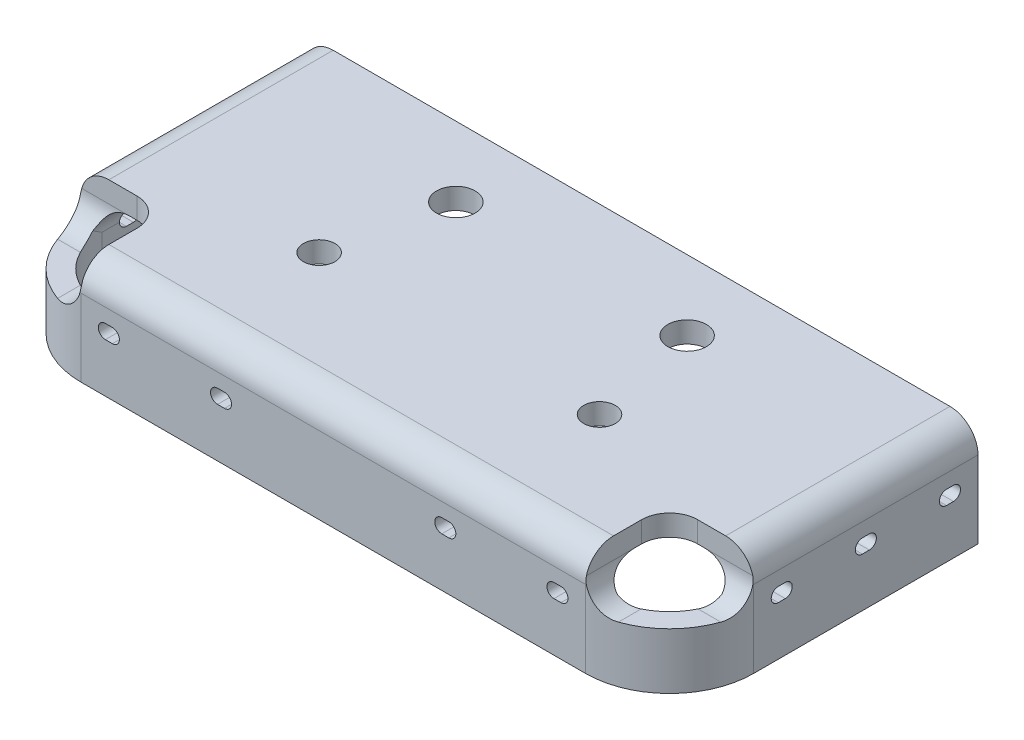
SolidWorks part; units mm, degrees
ref_plane "Front Plane" through (0, 0, 0) normal (0, 0, 1) x (1, 0, 0)
ref_plane "Top Plane" through (0, 0, 0) normal (0, 1, 0) x (1, 0, 0)
ref_plane "Right Plane" through (0, 0, 0) normal (1, 0, 0) x (0, 0, -1)
sketch "Sketch1" plane through (0, 0, 0) normal (0, 1, 0) x (1, 0, 0)
  line L0 (-41.275, 0) -> (41.275, 0) construction
  line L5 (-41.275, 25.4) -> (41.275, 25.4)
  line L6 (-41.275, 25.4) -> (-41.275, -25.4) construction
  line L7 (-41.275, -25.4) -> (41.275, -25.4) construction
  line L8 (41.275, 25.4) -> (41.275, -25.4) construction
  line L9 (-76.2, 25.4) -> (-76.2, -25.4)
  line L10 (-57.15, -44.45) -> (57.15, -44.45)
  line L11 (76.2, -25.4) -> (76.2, 25.4)
  line L12 (0, -25.4) -> (0, -44.45) construction
  line L13 (-41.275, 0) -> (-76.2, 0) construction
  line L14 (41.275, 0) -> (76.2, 0) construction
  line L15 (-41.275, 25.4) -> (-76.2, 25.4)
  line L16 (41.275, 25.4) -> (76.2, 25.4)
  line L17 (57.15, -44.45) -> (57.15, -25.4)
  line L18 (57.15, -25.4) -> (76.2, -25.4)
  line L19 (-76.2, -25.4) -> (-57.15, -25.4)
  line L20 (-57.15, -25.4) -> (-57.15, -44.45)
  arc A0 (-76.2, -25.4) -> (-57.15, -44.45) centre (-57.15, -25.4) ccw construction
  arc A1 (57.15, -44.45) -> (76.2, -25.4) centre (57.15, -25.4) ccw construction
  dimension "D4" = 19.05
  dimension "D1" = 50.8
  dimension "D2" = 152.4
  dimension "D3" = 69.85
  dimension "D5" = 82.55
extrude "Boss-Extrude1" add sketch "Sketch1" along normal blind 4.7625
sketch "Sketch9" plane through (0, 4.7625, 0) normal (0, 1, 0) x (1, 0, 0)
  line L0 (0, 9.525) -> (0, -15.875) construction
  line L1 (-31.75, -15.875) -> (31.75, -15.875) construction
  line L2 (-26.1937, 9.525) -> (26.1937, 9.525) construction
  point P7 (0, 0)
  point P8 (0, 0)
  dimension "D1" = 15.875
  dimension "D2" = 9.525
  dimension "D3" = 52.3875
  dimension "D4" = 63.5
hole_wizard "5/16 Clearance Hole1" positions "Sketch10" profile "Sketch11" hole size "5/16" standard "ANSI Inch" end condition through all
sketch "Sketch10" plane through (0, 4.7625, 0) normal (0, 1, 0) x (1, 0, 0)
  point P0 (-26.1937, 9.525)
  point P3 (26.1937, 9.525)
sketch "Sketch11" plane through (-26.1937, 4.7625, -9.525) normal (1, 0, 0) x (0, 0, 1)
  line L0 (0, 0) -> (0, 4.7625)
  line L1 (0, 4.7625) -> (4.365, 4.7625)
  line L2 (4.365, 4.7625) -> (4.365, 0)
  line L5 (4.365, 0) -> (0, 0)
  line L11 (0, -6.35) -> (0, 107.95) construction
  dimension "Thru Hole Dia." = 8.73
  dimension "Thru Hole Depth" = 4.7625
hole_wizard "1/4 Clearance Hole1" positions "Sketch12" profile "Sketch13" hole size "1/4" standard "ANSI Inch" end condition through all
sketch "Sketch12" plane through (0, 4.7625, 0) normal (0, 1, 0) x (1, 0, 0)
  point P0 (-31.75, -15.875)
  point P3 (31.75, -15.875)
sketch "Sketch13" plane through (-31.75, 4.7625, 15.875) normal (1, 0, 0) x (0, 0, 1)
  line L0 (0, 0) -> (0, 4.7625)
  line L1 (0, 4.7625) -> (3.5712, 4.7625)
  line L2 (3.5712, 4.7625) -> (3.5712, 0)
  line L5 (3.5712, 0) -> (0, 0)
  line L11 (0, -6.35) -> (0, 107.95) construction
  dimension "Thru Hole Dia." = 7.1425
  dimension "Thru Hole Depth" = 4.7625
sketch "Sketch2" plane through (0, 0, 0) normal (0, 1, 0) x (1, 0, 0)
  line L0 (76.2, -25.4) -> (76.2, 25.4) construction
  line L1 (-57.15, -44.45) -> (57.15, -44.45) construction
  line L2 (-76.2, 25.4) -> (-76.2, -25.4) construction
  line L3 (76.2, -25.4) -> (76.2, 25.4)
  line L4 (-57.15, -44.45) -> (57.15, -44.45)
  line L5 (-76.2, 25.4) -> (-76.2, -25.4)
  line L6 (-71.4375, 25.4) -> (-71.4375, -25.4)
  line L7 (-57.15, -39.6875) -> (57.15, -39.6875)
  line L8 (71.4375, -25.4) -> (71.4375, 25.4)
  line L9 (-76.2, 25.4) -> (-71.4375, 25.4)
  line L10 (76.2, 25.4) -> (71.4375, 25.4)
  arc A0 (57.15, -44.45) -> (76.2, -25.4) centre (57.15, -25.4) ccw construction
  arc A1 (-76.2, -25.4) -> (-57.15, -44.45) centre (-57.15, -25.4) ccw construction
  arc A2 (57.15, -44.45) -> (76.2, -25.4) centre (57.15, -25.4) ccw
  arc A3 (-76.2, -25.4) -> (-57.15, -44.45) centre (-57.15, -25.4) ccw
  arc A4 (-71.4375, -25.4) -> (-57.15, -39.6875) centre (-57.15, -25.4) ccw
  arc A5 (57.15, -39.6875) -> (71.4375, -25.4) centre (57.15, -25.4) ccw
  dimension "D1" = 4.7625
extrude "Boss-Extrude2" add sketch "Sketch2" against normal blind 19.05
sketch "Sketch18" plane through (0, 0, 0) normal (0, 1, 0) x (1, 0, 0)
  line L0 (76.2, -25.4) -> (71.4375, -25.4) construction
  line L1 (57.15, -39.6875) -> (57.15, -44.45) construction
  line L2 (-57.15, -44.45) -> (-57.15, -39.6875) construction
  line L3 (-71.4375, -25.4) -> (-76.2, -25.4) construction
  line L4 (76.2, -25.4) -> (71.4375, -25.4)
  line L5 (57.15, -39.6875) -> (57.15, -44.45)
  line L6 (-57.15, -44.45) -> (-57.15, -39.6875)
  line L7 (-71.4375, -25.4) -> (-76.2, -25.4)
  arc A0 (57.15, -39.6875) -> (71.4375, -25.4) centre (57.15, -25.4) ccw construction
  arc A1 (57.15, -44.45) -> (76.2, -25.4) centre (57.15, -25.4) ccw construction
  arc A2 (-71.4375, -25.4) -> (-57.15, -39.6875) centre (-57.15, -25.4) ccw construction
  arc A3 (-76.2, -25.4) -> (-57.15, -44.45) centre (-57.15, -25.4) ccw construction
  arc A4 (57.15, -39.6875) -> (71.4375, -25.4) centre (57.15, -25.4) ccw
  arc A5 (57.15, -44.45) -> (76.2, -25.4) centre (57.15, -25.4) ccw
  arc A6 (-71.4375, -25.4) -> (-57.15, -39.6875) centre (-57.15, -25.4) ccw
  arc A7 (-76.2, -25.4) -> (-57.15, -44.45) centre (-57.15, -25.4) ccw
extrude "Cut-Extrude3" cut sketch "Sketch18" against normal offset from surface (6.35 mm away) 12.7 up to face at (0, -19.05, 15.1737)
fillet "Fillet4" radius 6.35 8 edges at (-76.2, 4.7625, 0) (76.2, 4.7625, 0) (0, 4.7625, 44.45) (71.4375, 0, 0) (-71.4375, 0, 0) (0, 0, 39.6875) (-57.15, 2.3813, 25.4) (57.15, 2.3813, 25.4)
fillet "Fillet5" radius 6.35 4 edges at (73.8188, -6.35, 25.4) (-57.15, -6.35, 42.0687) (-73.8188, -6.35, 25.4) (57.15, -6.35, 42.0687)
sketch "Sketch15" plane through (0, 0, 0) normal (1, 0, 0) x (0, 0, -1)
  line L0 (-18.2563, -6.35) -> (-19.8438, -6.35) construction
  line L1 (-18.2563, -7.9375) -> (-19.8438, -7.9375)
  line L2 (-18.2563, -4.7625) -> (-19.8438, -4.7625)
  line L3 (-25.4, -19.05) -> (25.4, -19.05) construction
  line L4 (0.7937, -6.35) -> (-0.7937, -6.35) construction
  line L5 (0.7937, -7.9375) -> (-0.7937, -7.9375)
  line L6 (0.7937, -4.7625) -> (-0.7937, -4.7625)
  line L7 (19.8438, -6.35) -> (18.2563, -6.35) construction
  line L8 (19.8438, -7.9375) -> (18.2563, -7.9375)
  line L9 (19.8438, -4.7625) -> (18.2563, -4.7625)
  arc A0 (-18.2563, -7.9375) -> (-18.2563, -4.7625) centre (-18.2563, -6.35) ccw
  arc A1 (-19.8438, -4.7625) -> (-19.8438, -7.9375) centre (-19.8438, -6.35) ccw
  arc A2 (0.7937, -7.9375) -> (0.7937, -4.7625) centre (0.7937, -6.35) ccw
  arc A3 (-0.7937, -4.7625) -> (-0.7937, -7.9375) centre (-0.7937, -6.35) ccw
  arc A4 (19.8438, -7.9375) -> (19.8438, -4.7625) centre (19.8438, -6.35) ccw
  arc A5 (18.2563, -4.7625) -> (18.2563, -7.9375) centre (18.2563, -6.35) ccw
  point P2 (-19.05, -6.35)
  point P10 (19.8438, -4.7625)
  point P13 (0, -6.35)
  point P20 (19.05, -6.35)
  point P25 (0, 0)
  dimension "D1" = 1.5875
  dimension "D2" = 1.5875
  dimension "D3" = 19.05
  dimension "D4" = 12.7
  dimension "D5" = 3
extrude "Cut-Extrude1" cut sketch "Sketch15" against normal through all both and the other way through all
sketch "Sketch16" plane through (0, 0, 0) normal (0, 0, 1) x (1, 0, 0)
  line L0 (-51.5938, -6.35) -> (-50.0062, -6.35) construction
  line L1 (-51.5938, -4.7625) -> (-50.0062, -4.7625)
  line L2 (-51.5938, -7.9375) -> (-50.0062, -7.9375)
  line L3 (-57.15, -19.05) -> (57.15, -19.05) construction
  line L4 (-26.1938, -6.35) -> (-24.6062, -6.35) construction
  line L5 (-26.1938, -4.7625) -> (-24.6062, -4.7625)
  line L6 (-26.1938, -7.9375) -> (-24.6062, -7.9375)
  line L10 (24.6062, -6.35) -> (26.1937, -6.35) construction
  line L11 (24.6062, -4.7625) -> (26.1937, -4.7625)
  line L12 (24.6062, -7.9375) -> (26.1937, -7.9375)
  line L13 (50.0062, -6.35) -> (51.5938, -6.35) construction
  line L14 (50.0062, -4.7625) -> (51.5938, -4.7625)
  line L15 (50.0062, -7.9375) -> (51.5937, -7.9375)
  line L64 (-0.7938, -6.35) -> (0.7938, -6.35) construction
  line L65 (-0.7938, -4.7625) -> (0.7938, -4.7625)
  line L66 (-0.7938, -7.9375) -> (0.7938, -7.9375)
  line L67 (-0.7938, -6.35) -> (0.7938, -6.35) construction
  line L68 (-0.7938, -4.7625) -> (0.7938, -4.7625)
  line L69 (-0.7938, -7.9375) -> (0.7937, -7.9375)
  arc A0 (-51.5938, -4.7625) -> (-51.5938, -7.9375) centre (-51.5938, -6.35) ccw
  arc A1 (-50.0062, -7.9375) -> (-50.0062, -4.7625) centre (-50.0062, -6.35) ccw
  arc A2 (-26.1938, -4.7625) -> (-26.1938, -7.9375) centre (-26.1938, -6.35) ccw
  arc A3 (-24.6062, -7.9375) -> (-24.6062, -4.7625) centre (-24.6062, -6.35) ccw
  arc A6 (24.6062, -4.7625) -> (24.6062, -7.9375) centre (24.6062, -6.35) ccw
  arc A7 (26.1937, -7.9375) -> (26.1937, -4.7625) centre (26.1937, -6.35) ccw
  arc A8 (50.0062, -4.7625) -> (50.0062, -7.9375) centre (50.0062, -6.35) ccw
  arc A9 (51.5937, -7.9375) -> (51.5938, -4.7625) centre (51.5938, -6.35) ccw
  arc A44 (-0.7938, -4.7625) -> (-0.7938, -7.9375) centre (-0.7938, -6.35) ccw
  arc A45 (0.7937, -7.9375) -> (0.7938, -4.7625) centre (0.7938, -6.35) ccw
  point P2 (-50.8, -6.35)
  point P14 (-25.4, -6.35)
  point P21 (0, -6.35)
  point P28 (25.4, -6.35)
  point P35 (50.8, -6.35)
  point P42 (0, -6.35)
  point P49 (0, -6.35)
  point P56 (0, -6.35)
  point P63 (0, -6.35)
  point P70 (0, -6.35)
  point P77 (0, -6.35)
  point P84 (0, -6.35)
  point P91 (0, -6.35)
  point P98 (0, -6.35)
  point P105 (0, -6.35)
  point P112 (0, -6.35)
  point P119 (0, -6.35)
  point P126 (0, -6.35)
  point P133 (0, -6.35)
  point P140 (0, -6.35)
  point P147 (0, -6.35)
  point P154 (0, -6.35)
  point P161 (0, -6.35)
  dimension "D1" = 1.5875
  dimension "D2" = 1.5875
  dimension "D3" = 50.8
  dimension "D4" = 12.7
  dimension "D6" = 50.8
  dimension "D5" = 5
extrude "Cut-Extrude2" cut sketch "Sketch16" against normal through all both and the other way through all
equation "\"D6@Sketch16\"=\"D3@Sketch16\""
